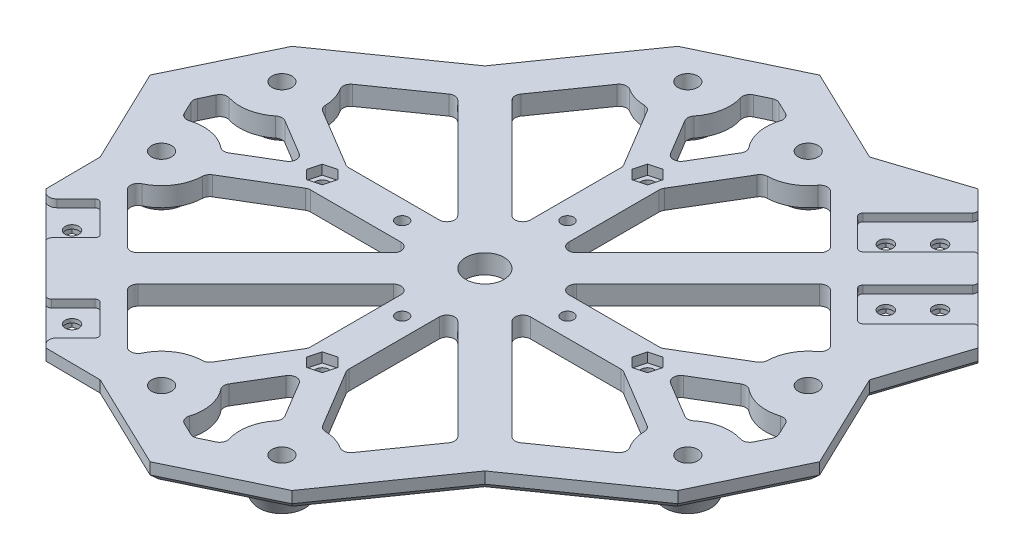
SolidWorks part; units mm, degrees
ref_plane "Front Plane" through (0, 0, 0) normal (0, 0, 1) x (1, 0, 0)
ref_plane "Top Plane" through (0, 0, 0) normal (0, 1, 0) x (1, 0, 0)
ref_plane "Right Plane" through (0, 0, 0) normal (1, 0, 0) x (0, 0, -1)
sketch "Sketch1" plane through (0, 0, 0) normal (0, 1, 0) x (1, 0, 0)
  line L0 (-15.705, 68.65) -> (15.705, 68.65) construction
  line L1 (0, 68.65) -> (0, 0) construction
  line L10 (-15.705, 68.65) -> (0, 87.35) construction
  line L11 (-25.0004, 75.3528) -> (0, 87.35)
  line L12 (0, 87.35) -> (25.0004, 75.3528)
  line L26 (-25.0004, 75.3528) -> (-15.705, 68.65) construction
  line L27 (0, 87.35) -> (15.705, 68.65) construction
  line L28 (-15.705, 68.65) -> (15.705, 68.65) construction
  line L30 (15.705, 68.65) -> (25.0004, 75.3528) construction
  line L31 (75.3528, 25.0004) -> (87.35, 0)
  line L32 (87.35, 0) -> (75.3528, -25.0004)
  line L33 (68.65, 15.705) -> (68.65, -15.705) construction
  line L34 (68.65, 15.705) -> (87.35, 0) construction
  line L36 (75.3528, 25.0004) -> (68.65, 15.705) construction
  line L37 (87.35, 0) -> (68.65, -15.705) construction
  line L38 (68.65, 15.705) -> (68.65, -15.705) construction
  line L39 (68.65, -15.705) -> (75.3528, -25.0004) construction
  line L40 (25.0004, -75.3528) -> (0, -87.35)
  line L41 (0, -87.35) -> (-25.0004, -75.3528)
  line L42 (15.705, -68.65) -> (-15.705, -68.65) construction
  line L43 (15.705, -68.65) -> (0, -87.35) construction
  line L44 (25.0004, -75.3528) -> (45.7527, -45.7527)
  line L45 (25.0004, -75.3528) -> (15.705, -68.65) construction
  line L46 (0, -87.35) -> (-15.705, -68.65) construction
  line L47 (15.705, -68.65) -> (-15.705, -68.65) construction
  line L48 (-15.705, -68.65) -> (-25.0004, -75.3528) construction
  line L49 (-75.3528, -25.0004) -> (-87.35, 0)
  line L50 (-87.35, 0) -> (-75.3528, 25.0004)
  line L51 (-68.65, -15.705) -> (-68.65, 15.705) construction
  line L52 (-68.65, -15.705) -> (-87.35, 0) construction
  line L53 (45.7527, -45.7527) -> (75.3528, -25.0004)
  line L54 (-75.3528, -25.0004) -> (-68.65, -15.705) construction
  line L55 (-87.35, 0) -> (-68.65, 15.705) construction
  line L56 (-68.65, -15.705) -> (-68.65, 15.705) construction
  line L57 (-68.65, 15.705) -> (-75.3528, 25.0004) construction
  line L58 (-75.3528, 25.0004) -> (-45.7527, 45.7527)
  line L59 (-45.7527, 45.7527) -> (-25.0004, 75.3528)
  line L62 (-75.3528, -25.0004) -> (-75.2258, -39.2695)
  line L66 (-39.2695, -75.2258) -> (-25.0004, -75.3528)
  line L67 (-75.2258, -39.2695) -> (-39.2695, -75.2258)
  line L68 (-75.3528, -25.0004) -> (-25.0004, -75.3528) construction
  line L69 (46.3472, 82.3036) -> (82.3036, 46.3472)
  line L70 (-45.7527, 45.7527) -> (45.7527, -45.7527) construction
  line L71 (25.0004, 75.3528) -> (46.3472, 82.3036)
  line L75 (82.3036, 46.3472) -> (75.3528, 25.0004)
  line L76 (64.3254, 64.3254) -> (50.1766, 50.1766) construction
  line L77 (25.0004, 75.3528) -> (75.3528, 25.0004) construction
  line L78 (-57.2477, -57.2477) -> (-50.1766, -50.1766) construction
  circle A0 centre (-15.705, 68.65) radius 2.6
  circle A1 centre (15.705, 68.65) radius 2.6
  circle A2 centre (68.65, 15.705) radius 2.6
  circle A3 centre (68.65, -15.705) radius 2.6
  circle A4 centre (15.705, -68.65) radius 2.6
  circle A5 centre (-15.705, -68.65) radius 2.6
  circle A6 centre (-68.65, -15.705) radius 2.6
  circle A7 centre (-68.65, 15.705) radius 2.6
  point P4 (0, 68.65)
  point P42 (0, 0)
  dimension "D1" = 5.2
  dimension "D2" = 31.41
  dimension "D3" = 68.65
  dimension "D5" = 24.42
  dimension "D6" = 10
  dimension "D7" = 11.46
  dimension "D8" = 36.15
  dimension "D9" = 4
  dimension "D4" = 27.73
  dimension "D12" = 50.85
  dimension "D13" = 22.45
  dimension "D15" = 50.85
extrude "Boss-Extrude1" add sketch "Sketch1" along normal blind 5
ref_axis "Axis1" through (-15.705, 5, -68.65) along (0, -1, 0)
ref_plane "Plane1" through (14.012, 0, -6.7241) normal (0.9016, 0, -0.4326) x (0, -1, 0)
sketch "Sketch4" plane through (14.012, 0, -6.7241) normal (0.9016, 0, -0.4326) x (0, -1, 0)
  line L0 (0, 73.1871) -> (4, 73.1871)
  line L1 (4, 73.1871) -> (4, 74.6871)
  line L2 (4, 74.6871) -> (0, 76.6871)
  line L3 (0, 76.6871) -> (0, 73.1871)
  line L4 (-5, 68.6871) -> (0, 68.6871) construction
  point P0 (0, 68.6871)
  dimension "D1" = 4
  dimension "D2" = 8
  dimension "D3" = 4.5
  dimension "D4" = 6
revolve "Revolve1" add sketch "Sketch4" angle 360 about axis through (-15.705, 5, -68.65) along (0, -1, 0)
ref_plane "Plane2" through (0, 0, 0) normal (1, 0, 0) x (0, 0, -1)
mirror "Mirror1" about plane through (0, 0, 0) normal (1, 0, 0) of "Revolve1"
ref_axis "Axis3" through (0, 0, 0) along (0, -1, 0)
pattern_circular "CirPattern1" count 4 every 90 about axis through (0, 0, 0) along (0, -1, 0) of "Revolve1", "Mirror1"
chamfer "Chamfer2" distance 2 angle 45 16 edges at (-32.1349, 0, 75.2893) (-12.5002, 0, 81.3514) (12.5002, 0, 81.3514) (35.3765, 0, 60.5527) (60.5527, 0, 35.3765) (81.3514, 0, 12.5002) (81.3514, 0, -12.5002) (78.8282, 0, -35.6738) (35.6738, 0, -78.8282) (12.5002, 0, -81.3514) (-12.5002, 0, -81.3514) (-35.3765, 0, -60.5527) (-60.5527, 0, -35.3765) (-81.3514, 0, -12.5002) (-81.3514, 0, 12.5002) (-75.2893, 0, 32.1349)
sketch "Sketch5" plane through (0, 0, 0) normal (0, -1, 0) x (1, 0, 0)
  line L0 (-57.2477, 57.2477) -> (64.3254, -64.3254) construction
  line L3 (44.3168, 44.3168) -> (-44.3168, -44.3168) construction
  line L4 (-21.5668, 0) -> (0, 21.5668) construction
  line L5 (0, 21.5668) -> (21.5668, 0) construction
  line L6 (21.5668, 0) -> (0, -21.5668) construction
  line L7 (0, -21.5668) -> (-21.5668, 0) construction
  line L10 (-73.2078, 41.2875) -> (-41.2875, 73.2078) construction
  line L11 (80.7169, -47.934) -> (47.934, -80.7169) construction
  circle A0 centre (0, 21.5668) radius 1.6
  circle A1 centre (-21.5668, 0) radius 1.6
  circle A2 centre (0, -21.5668) radius 1.6
  circle A3 centre (21.5668, 0) radius 1.6
  dimension "D4" = 3.2
  dimension "D1" = 30.5
  dimension "D2" = 15.25
  dimension "D3" = 15.25
extrude "Cut-Extrude1" cut sketch "Sketch5" against normal through all
sketch "Sketch6" plane through (0, 0, 0) normal (0, -1, 0) x (1, 0, 0)
  line L0 (44.3168, 44.3168) -> (-44.3168, -44.3168) construction
  line L1 (2.0412, 23.608) -> (-0.7471, 24.3551)
  line L2 (-0.7471, 24.3551) -> (-2.7884, 22.3139)
  line L3 (-2.7884, 22.3139) -> (-2.0412, 19.5255)
  line L4 (-2.0412, 19.5255) -> (0.7471, 18.7784)
  line L5 (0.7471, 18.7784) -> (2.7884, 20.8196)
  line L6 (2.7884, 20.8196) -> (2.0412, 23.608)
  line L7 (23.608, 2.0412) -> (20.8196, 2.7884)
  line L8 (20.8196, 2.7884) -> (18.7784, 0.7471)
  line L9 (18.7784, 0.7471) -> (19.5255, -2.0412)
  line L10 (19.5255, -2.0412) -> (22.3139, -2.7884)
  line L11 (22.3139, -2.7884) -> (24.3551, -0.7471)
  line L12 (24.3551, -0.7471) -> (23.608, 2.0412)
  line L13 (-19.5255, 2.0412) -> (-22.3139, 2.7884)
  line L14 (-22.3139, 2.7884) -> (-24.3551, 0.7471)
  line L15 (-24.3551, 0.7471) -> (-23.608, -2.0412)
  line L16 (-23.608, -2.0412) -> (-20.8196, -2.7884)
  line L17 (-20.8196, -2.7884) -> (-18.7784, -0.7471)
  line L18 (-18.7784, -0.7471) -> (-19.5255, 2.0412)
  line L19 (-0.7471, -18.7784) -> (-2.7884, -20.8196)
  line L20 (-2.7884, -20.8196) -> (-2.0412, -23.608)
  line L21 (-2.0412, -23.608) -> (0.7471, -24.3551)
  line L22 (0.7471, -24.3551) -> (2.7884, -22.3139)
  line L23 (2.7884, -22.3139) -> (2.0412, -19.5255)
  line L24 (2.0412, -19.5255) -> (-0.7471, -18.7784)
  circle A0 centre (0, 21.5668) radius 2.5 construction
  circle A1 centre (21.5668, 0) radius 2.5 construction
  circle A2 centre (-21.5668, 0) radius 2.5 construction
  circle A3 centre (0, -21.5668) radius 2.5 construction
  dimension "D1" = 5
extrude "Cut-Extrude2" cut sketch "Sketch6" against normal blind 2.5
sketch "Sketch8" plane through (0, 5, 0) normal (0, 1, 0) x (1, 0, 0)
  line L0 (-64.4601, -43.2469) -> (-43.2469, -64.4601) construction
  line L1 (-75.2258, -39.2695) -> (-39.2695, -75.2258) construction
  line L2 (-53.8535, -53.8535) -> (-57.2477, -57.2477) construction
  line L3 (51.9511, 66.8003) -> (66.8003, 51.9511) construction
  line L4 (44.88, 59.7292) -> (59.7292, 44.88) construction
  line L5 (82.3036, 46.3472) -> (46.3472, 82.3036) construction
  line L6 (64.3254, 64.3254) -> (59.3757, 59.3757) construction
  line L7 (59.3757, 59.3757) -> (52.3046, 52.3046) construction
  circle A0 centre (-64.4601, -43.2469) radius 1.8
  circle A1 centre (-43.2469, -64.4601) radius 1.8
  circle A2 centre (51.9511, 66.8003) radius 1.8
  circle A3 centre (44.88, 59.7292) radius 1.8
  circle A4 centre (66.8003, 51.9511) radius 1.8
  circle A5 centre (59.7292, 44.88) radius 1.8
  dimension "D1" = 3.6
  dimension "D4" = 3.6
  dimension "D2" = 4.8
  dimension "D3" = 30
  dimension "D5" = 7
  dimension "D6" = 17
  dimension "D7" = 21
  dimension "D8" = 21
extrude "Cut-Extrude3" cut sketch "Sketch8" against normal through all
sketch "Sketch9" plane through (0, 5, 0) normal (0, 1, 0) x (1, 0, 0)
  line L0 (-75.2258, -39.2695) -> (-72.9454, -41.5499) construction
  line L1 (-75.2258, -39.2695) -> (-39.2695, -75.2258) construction
  line L2 (-72.9454, -41.5499) -> (-65.8744, -34.4788)
  line L3 (-65.8744, -34.4788) -> (-57.1062, -43.2469)
  line L4 (-57.1062, -43.2469) -> (-64.1773, -50.318)
  line L5 (-64.1773, -50.318) -> (-50.318, -64.1773) construction
  line L6 (-50.318, -64.1773) -> (-43.2469, -57.1062)
  line L7 (-43.2469, -57.1062) -> (-34.4788, -65.8744)
  line L8 (-34.4788, -65.8744) -> (-41.5499, -72.9454)
  line L9 (-41.5499, -72.9454) -> (-39.2695, -75.2258) construction
  line L10 (-72.9454, -41.5499) -> (-64.1773, -50.318)
  line L11 (-50.318, -64.1773) -> (-41.5499, -72.9454)
  line L12 (46.3472, 82.3036) -> (51.8096, 76.8412) construction
  line L13 (82.3036, 46.3472) -> (46.3472, 82.3036) construction
  line L14 (51.8096, 76.8412) -> (36.1119, 61.1435)
  line L15 (36.1119, 61.1435) -> (44.88, 52.3753)
  line L16 (44.88, 52.3753) -> (60.5778, 68.0731)
  line L17 (60.5778, 68.0731) -> (68.0731, 60.5778) construction
  line L18 (68.0731, 60.5778) -> (52.3753, 44.88)
  line L19 (52.3753, 44.88) -> (61.1435, 36.1119)
  line L20 (61.1435, 36.1119) -> (76.8412, 51.8096)
  line L21 (76.8412, 51.8096) -> (82.3036, 46.3472) construction
  line L22 (51.8096, 76.8412) -> (60.5778, 68.0731)
  line L23 (68.0731, 60.5778) -> (76.8412, 51.8096)
  dimension "D1" = 12.4
  dimension "D2" = 12.4
  dimension "D3" = 19.6
  dimension "D4" = 10
  dimension "D5" = 10
  dimension "D6" = 10.6
  dimension "D7" = 12.4
  dimension "D8" = 12.4
  dimension "D9" = 22.2
  dimension "D10" = 22.2
extrude "Cut-Extrude4" cut sketch "Sketch9" against normal blind 2
sketch "Sketch11" plane through (0, 0, 0) normal (0, -1, 0) x (1, 0, 0)
  line L0 (-73.2078, 41.2875) -> (-41.2875, 73.2078) construction
  line L1 (-40.8995, 66.8076) -> (-44.1062, 67.6668)
  line L2 (-44.1062, 67.6668) -> (-46.4536, 65.3194)
  line L3 (-46.4536, 65.3194) -> (-45.5944, 62.1127)
  line L4 (-45.5944, 62.1127) -> (-42.3877, 61.2535)
  line L5 (-42.3877, 61.2535) -> (-40.0403, 63.6009)
  line L6 (-40.0403, 63.6009) -> (-40.8995, 66.8076)
  line L7 (-65.3194, 46.4536) -> (-67.6668, 44.1062)
  line L8 (-67.6668, 44.1062) -> (-66.8076, 40.8995)
  line L9 (-66.8076, 40.8995) -> (-63.6009, 40.0403)
  line L10 (-63.6009, 40.0403) -> (-61.2535, 42.3877)
  line L11 (-61.2535, 42.3877) -> (-62.1127, 45.5944)
  line L12 (-62.1127, 45.5944) -> (-65.3194, 46.4536)
  line L13 (80.7169, -47.934) -> (47.934, -80.7169) construction
  line L14 (62.0767, -42.5326) -> (58.87, -41.6734)
  line L15 (58.87, -41.6734) -> (56.5226, -44.0208)
  line L16 (56.5226, -44.0208) -> (57.3818, -47.2274)
  line L17 (57.3818, -47.2274) -> (60.5885, -48.0866)
  line L18 (60.5885, -48.0866) -> (62.9359, -45.7392)
  line L19 (62.9359, -45.7392) -> (62.0767, -42.5326)
  line L20 (69.1477, -49.6036) -> (65.9411, -48.7444)
  line L21 (65.9411, -48.7444) -> (63.5937, -51.0919)
  line L22 (63.5937, -51.0919) -> (64.4529, -54.2985)
  line L23 (64.4529, -54.2985) -> (67.6595, -55.1577)
  line L24 (67.6595, -55.1577) -> (70.007, -52.8103)
  line L25 (70.007, -52.8103) -> (69.1477, -49.6036)
  line L26 (54.2985, -64.4529) -> (51.0919, -63.5937)
  line L27 (51.0919, -63.5937) -> (48.7444, -65.9411)
  line L28 (48.7444, -65.9411) -> (49.6036, -69.1477)
  line L29 (49.6036, -69.1477) -> (52.8103, -70.007)
  line L30 (52.8103, -70.007) -> (55.1577, -67.6595)
  line L31 (55.1577, -67.6595) -> (54.2985, -64.4529)
  line L32 (47.2274, -57.3818) -> (44.0208, -56.5226)
  line L33 (44.0208, -56.5226) -> (41.6734, -58.87)
  line L34 (41.6734, -58.87) -> (42.5326, -62.0767)
  line L35 (42.5326, -62.0767) -> (45.7392, -62.9359)
  line L36 (45.7392, -62.9359) -> (48.0866, -60.5885)
  line L37 (48.0866, -60.5885) -> (47.2274, -57.3818)
  circle A0 centre (-43.2469, 64.4601) radius 2.875 construction
  circle A1 centre (-64.4601, 43.2469) radius 2.875 construction
  circle A2 centre (59.7292, -44.88) radius 2.875 construction
  circle A3 centre (66.8003, -51.9511) radius 2.875 construction
  circle A4 centre (51.9511, -66.8003) radius 2.875 construction
  circle A5 centre (44.88, -59.7292) radius 2.875 construction
  dimension "D1" = 5.75
extrude "Cut-Extrude5" cut sketch "Sketch11" against normal blind 2
fillet "Fillet1" radius 1 14 edges at (-43.2469, 4, 57.1062) (-50.318, 4, 64.1773) (-34.4788, 4, 65.8744) (-57.1062, 4, 43.2469) (-64.1773, 4, 50.318) (-65.8744, 4, 34.4788) (60.5778, 4, -68.0731) (44.88, 4, -52.3753) (76.8412, 4, -51.8096) (61.1435, 4, -36.1119) (68.0731, 4, -60.5778) (52.3753, 4, -44.88) (51.8096, 4, -76.8412) (36.1119, 4, -61.1435)
fillet "Fillet2" radius 2 2 edges at (-41.5499, 4, 72.9454) (-72.9454, 4, 41.5499)
sketch "Sketch13" plane through (0, 5, 0) normal (0, 1, 0) x (1, 0, 0)
  line L0 (-45.7527, 45.7527) -> (0, 0) construction
  line L1 (0, 0) -> (64.3254, 64.3254) construction
  line L2 (67.366, 61.2849) -> (61.2849, 67.366) construction
  circle A0 centre (0, 42.4264) radius 1.8
  circle A1 centre (42.4264, 0) radius 1.8
  circle A2 centre (0, -42.4264) radius 1.8
  circle A3 centre (-42.4264, 0) radius 1.8
  dimension "D3" = 3.6
  dimension "D1" = 30
  dimension "D2" = 30
extrude "Cut-Extrude7" cut sketch "Sketch13" against normal through all
sketch "Sketch14" plane through (0, 5, 0) normal (0, 1, 0) x (1, 0, 0)
  line L0 (67.366, 61.2849) -> (61.2849, 67.366) construction
  line L1 (3.2066, 43.2856) -> (0.8592, 45.6331)
  line L2 (0.8592, 45.6331) -> (-2.3474, 44.7738)
  line L3 (-2.3474, 44.7738) -> (-3.2066, 41.5672)
  line L4 (-3.2066, 41.5672) -> (-0.8592, 39.2198)
  line L5 (-0.8592, 39.2198) -> (2.3474, 40.079)
  line L6 (2.3474, 40.079) -> (3.2066, 43.2856)
  line L7 (43.2856, 3.2066) -> (40.079, 2.3474)
  line L8 (40.079, 2.3474) -> (39.2198, -0.8592)
  line L9 (39.2198, -0.8592) -> (41.5672, -3.2066)
  line L10 (41.5672, -3.2066) -> (44.7738, -2.3474)
  line L11 (44.7738, -2.3474) -> (45.6331, 0.8592)
  line L12 (45.6331, 0.8592) -> (43.2856, 3.2066)
  line L13 (0.8592, -39.2198) -> (-2.3474, -40.079)
  line L14 (-2.3474, -40.079) -> (-3.2066, -43.2856)
  line L15 (-3.2066, -43.2856) -> (-0.8592, -45.6331)
  line L16 (-0.8592, -45.6331) -> (2.3474, -44.7738)
  line L17 (2.3474, -44.7738) -> (3.2066, -41.5672)
  line L18 (3.2066, -41.5672) -> (0.8592, -39.2198)
  line L19 (-39.2198, 0.8592) -> (-41.5672, 3.2066)
  line L20 (-41.5672, 3.2066) -> (-44.7738, 2.3474)
  line L21 (-44.7738, 2.3474) -> (-45.6331, -0.8592)
  line L22 (-45.6331, -0.8592) -> (-43.2856, -3.2066)
  line L23 (-43.2856, -3.2066) -> (-40.079, -2.3474)
  line L24 (-40.079, -2.3474) -> (-39.2198, 0.8592)
  circle A0 centre (0, 42.4264) radius 2.875 construction
  circle A1 centre (42.4264, 0) radius 2.875 construction
  circle A2 centre (0, -42.4264) radius 2.875 construction
  circle A3 centre (-42.4264, 0) radius 2.875 construction
  point P28 (-43.1705, 2.777)
  dimension "D1" = 5.75
extrude "Cut-Extrude8" cut sketch "Sketch14" against normal blind 2.5
sketch "Sketch15" plane through (0, 5, 0) normal (0, 1, 0) x (1, 0, 0)
  line L0 (0, 0) -> (0, 21.5668) construction
  line L1 (0, 21.5668) -> (0, 42.4264) construction
  line L2 (0, 42.4264) -> (-15.705, 68.65) construction
  line L3 (0, 42.4264) -> (15.705, 68.65) construction
  line L4 (0, 0) -> (-21.5668, 0) construction
  line L5 (-21.5668, 0) -> (-42.4264, 0) construction
  line L6 (-42.4264, 0) -> (-68.65, 15.705) construction
  line L7 (-42.4264, 0) -> (-68.65, -15.705) construction
  line L8 (0, 0) -> (-45.7527, 45.7527) construction
  line L9 (0, 0) -> (64.3254, 64.3254) construction
  line L10 (67.366, 61.2849) -> (61.2849, 67.366) construction
  line L11 (0, 0) -> (-57.2477, -57.2477) construction
  line L12 (-63.4702, -51.0251) -> (-51.0251, -63.4702) construction
  line L13 (-58.8522, 24.356) -> (-44.105, 34.695)
  line L14 (-41.5427, 34.4716) -> (-15.4853, 8.4142)
  line L16 (-16.8995, 5) -> (-40.4906, 5)
  line L17 (-41.5182, 5.2842) -> (-56.6831, 14.3662)
  line L18 (-45.7527, 45.7527) -> (-75.3528, 25.0004) construction
  line L19 (-74.2699, 4.1432) -> (-75.8429, 0.8653)
  line L20 (-75.8429, -0.8653) -> (-74.2699, -4.1432)
  line L21 (-59.4711, 7.2938) -> (-50.1572, 1.7158)
  line L22 (-50.1572, -1.7158) -> (-59.4711, -7.2938)
  line L23 (-75.3528, 25.0004) -> (-87.35, 0) construction
  line L24 (-87.35, 0) -> (-75.3528, -25.0004) construction
  line L25 (-34.695, 44.105) -> (-24.356, 58.8522)
  line L26 (-14.3662, 56.6831) -> (-5.2842, 41.5182)
  line L27 (-5, 40.4906) -> (-5, 16.8995)
  line L29 (-8.4142, 15.4853) -> (-34.4716, 41.5427)
  line L30 (-25.0004, 75.3528) -> (-45.7527, 45.7527) construction
  line L31 (-4.1432, 74.2699) -> (-0.8653, 75.8429)
  line L32 (0.8653, 75.8429) -> (4.1432, 74.2699)
  line L33 (-7.2938, 59.4711) -> (-1.7158, 50.1572)
  line L34 (1.7158, 50.1572) -> (7.2938, 59.4711)
  line L35 (0, 87.35) -> (-25.0004, 75.3528) construction
  line L36 (25.0004, 75.3528) -> (0, 87.35) construction
  line L37 (-56.6831, -14.3662) -> (-41.5182, -5.2842)
  line L38 (-40.4906, -5) -> (-16.8995, -5)
  line L40 (-15.4853, -8.4142) -> (-48.7624, -41.6913)
  line L41 (-51.5908, -41.6913) -> (-64.4417, -28.8404)
  line L42 (-57.8133, -42.5398) -> (-65.1672, -35.1859) construction
  line L44 (5, 40.4906) -> (5, 16.8995)
  line L47 (8.4142, 15.4853) -> (40.1424, 47.2135)
  line L48 (40.1424, 50.0419) -> (27.6887, 62.4955)
  line L49 (36.819, 60.4364) -> (44.1729, 53.0824) construction
  line L50 (5.2842, 41.5182) -> (14.3662, 56.6831)
  line L51 (40.4906, 5) -> (16.8995, 5)
  line L52 (15.4853, 8.4142) -> (47.2135, 40.1424)
  line L53 (50.0419, 40.1424) -> (62.4955, 27.6887)
  line L54 (41.5182, 5.2842) -> (56.6831, 14.3662)
  line L55 (59.4711, -7.2938) -> (50.1572, -1.7158)
  line L56 (74.2699, -4.1432) -> (75.8429, -0.8653)
  line L57 (75.8429, 0.8653) -> (74.2699, 4.1432)
  line L58 (50.1572, 1.7158) -> (59.4711, 7.2938)
  line L59 (44.105, -34.695) -> (58.8522, -24.356)
  line L60 (15.4853, -8.4142) -> (41.5427, -34.4716)
  line L61 (40.4906, -5) -> (16.8995, -5)
  line L62 (56.6831, -14.3662) -> (41.5182, -5.2842)
  line L63 (24.356, -58.8522) -> (34.695, -44.105)
  line L64 (5.2842, -41.5182) -> (14.3662, -56.6831)
  line L65 (5, -16.8995) -> (5, -40.4906)
  line L66 (34.4716, -41.5427) -> (8.4142, -15.4853)
  line L67 (7.2938, -59.4711) -> (1.7158, -50.1572)
  line L68 (-1.7158, -50.1572) -> (-7.2938, -59.4711)
  line L69 (-0.8653, -75.8429) -> (-4.1432, -74.2699)
  line L70 (4.1432, -74.2699) -> (0.8653, -75.8429)
  line L71 (-41.6913, -51.5908) -> (-28.8404, -64.4417)
  line L72 (-8.4142, -15.4853) -> (-41.6913, -48.7624)
  line L73 (-5, -40.4906) -> (-5, -16.8995)
  line L74 (-14.3662, -56.6831) -> (-5.2842, -41.5182)
  circle A0 centre (-68.65, 15.705) radius 11 construction
  circle A1 centre (-68.65, -15.705) radius 11 construction
  circle A2 centre (-15.705, 68.65) radius 11 construction
  circle A3 centre (15.705, 68.65) radius 11 construction
  circle A4 centre (0, 42.4264) radius 5 construction
  circle A5 centre (0, 21.5668) radius 5 construction
  circle A6 centre (-21.5668, 0) radius 5 construction
  circle A7 centre (-42.4264, 0) radius 5 construction
  arc A11 (-61.7527, 7.136) -> (-71.8796, 5.1898) centre (-68.65, 15.705) cw
  arc A12 (-61.7527, -7.136) -> (-71.8796, -5.1898) centre (-68.65, -15.705) ccw
  arc A16 (-7.136, 61.7527) -> (-5.1898, 71.8796) centre (-15.705, 68.65) ccw
  arc A17 (5.1898, 71.8796) -> (7.136, 61.7527) centre (15.705, 68.65) ccw
  arc A32 (-59.4711, 7.2938) -> (-61.7527, 7.136) centre (-60.4987, 5.578) ccw
  arc A33 (-50.1572, 1.7158) -> (-50.1572, -1.7158) centre (-51.1848, 0) cw
  arc A34 (-59.4711, -7.2938) -> (-61.7527, -7.136) centre (-60.4987, -5.578) cw
  arc A35 (-74.2699, -4.1432) -> (-71.8796, -5.1898) centre (-72.4668, -3.2779) ccw
  arc A36 (-75.8429, 0.8653) -> (-75.8429, -0.8653) centre (-74.0398, 0) ccw
  arc A37 (-74.2699, 4.1432) -> (-71.8796, 5.1898) centre (-72.4668, 3.2779) cw
  arc A54 (-1.7158, 50.1572) -> (1.7158, 50.1572) centre (0, 51.1848) ccw
  arc A55 (7.2938, 59.4711) -> (7.136, 61.7527) centre (5.578, 60.4987) ccw
  arc A56 (-7.2938, 59.4711) -> (-7.136, 61.7527) centre (-5.578, 60.4987) cw
  arc A57 (4.1432, 74.2699) -> (5.1898, 71.8796) centre (3.2779, 72.4668) cw
  arc A58 (-0.8653, 75.8429) -> (0.8653, 75.8429) centre (0, 74.0398) cw
  arc A59 (-5.1898, 71.8796) -> (-4.1432, 74.2699) centre (-3.2779, 72.4668) cw
  arc A128 (-63.8925, -25.623) -> (-57.6546, -16.0241) centre (-68.65, -15.705) ccw
  arc A129 (-57.6546, 16.0241) -> (-59.3881, 21.6394) centre (-68.65, 15.705) ccw
  arc A130 (-21.6394, 59.3881) -> (-16.0241, 57.6546) centre (-15.705, 68.65) ccw
  arc A131 (24.6484, 62.2457) -> (16.0241, 57.6546) centre (15.705, 68.65) cw
  arc A132 (40.1424, 47.2135) -> (40.1424, 50.0419) centre (38.7282, 48.6277) ccw
  arc A133 (27.6887, 62.4955) -> (24.6484, 62.2457) centre (26.2745, 61.0813) ccw
  arc A134 (16.0241, 57.6546) -> (14.3662, 56.6831) centre (16.0821, 55.6555) ccw
  arc A135 (5, 40.4906) -> (5.2842, 41.5182) centre (7, 40.4906) cw
  arc A136 (8.4142, 15.4853) -> (5, 16.8995) centre (7, 16.8995) cw
  arc A137 (-5, 16.8995) -> (-8.4142, 15.4853) centre (-7, 16.8995) cw
  arc A138 (-5, 40.4906) -> (-5.2842, 41.5182) centre (-7, 40.4906) ccw
  arc A139 (-16.0241, 57.6546) -> (-14.3662, 56.6831) centre (-16.0821, 55.6555) cw
  arc A140 (-24.356, 58.8522) -> (-21.6394, 59.3881) centre (-22.7183, 57.7041) cw
  arc A141 (-34.4716, 41.5427) -> (-34.695, 44.105) centre (-33.0574, 42.9569) cw
  arc A142 (-64.4417, -28.8404) -> (-63.8925, -25.623) centre (-63.0275, -27.4262) cw
  arc A143 (-51.5908, -41.6913) -> (-48.7624, -41.6913) centre (-50.1766, -40.2771) ccw
  arc A144 (-15.4853, -8.4142) -> (-16.8995, -5) centre (-16.8995, -7) ccw
  arc A145 (-40.4906, -5) -> (-41.5182, -5.2842) centre (-40.4906, -7) ccw
  arc A146 (-40.4906, 5) -> (-41.5182, 5.2842) centre (-40.4906, 7) cw
  arc A147 (-16.8995, 5) -> (-15.4853, 8.4142) centre (-16.8995, 7) ccw
  arc A148 (-41.5427, 34.4716) -> (-44.105, 34.695) centre (-42.9569, 33.0574) ccw
  arc A149 (-59.3881, 21.6394) -> (-58.8522, 24.356) centre (-57.7041, 22.7183) cw
  arc A150 (-56.6831, 14.3662) -> (-57.6546, 16.0241) centre (-55.6555, 16.0821) cw
  arc A151 (-57.6546, -16.0241) -> (-56.6831, -14.3662) centre (-55.6555, -16.0821) cw
  arc A152 (15.4853, 8.4142) -> (16.8995, 5) centre (16.8995, 7) ccw
  arc A153 (47.2135, 40.1424) -> (50.0419, 40.1424) centre (48.6277, 38.7282) cw
  arc A154 (62.4955, 27.6887) -> (62.2457, 24.6484) centre (61.0813, 26.2745) cw
  arc A155 (62.2457, 24.6484) -> (57.6546, 16.0241) centre (68.65, 15.705) ccw
  arc A156 (57.6546, 16.0241) -> (56.6831, 14.3662) centre (55.6555, 16.0821) cw
  arc A157 (40.4906, 5) -> (41.5182, 5.2842) centre (40.4906, 7) ccw
  arc A158 (59.4711, -7.2938) -> (61.7527, -7.136) centre (60.4987, -5.578) ccw
  arc A159 (61.7527, -7.136) -> (71.8796, -5.1898) centre (68.65, -15.705) cw
  arc A160 (71.8796, -5.1898) -> (74.2699, -4.1432) centre (72.4668, -3.2779) ccw
  arc A161 (75.8429, -0.8653) -> (75.8429, 0.8653) centre (74.0398, 0) ccw
  arc A162 (74.2699, 4.1432) -> (71.8796, 5.1898) centre (72.4668, 3.2779) ccw
  arc A163 (71.8796, 5.1898) -> (61.7527, 7.136) centre (68.65, 15.705) cw
  arc A164 (59.4711, 7.2938) -> (61.7527, 7.136) centre (60.4987, 5.578) cw
  arc A165 (50.1572, -1.7158) -> (50.1572, 1.7158) centre (51.1848, 0) cw
  arc A166 (59.3881, -21.6394) -> (57.6546, -16.0241) centre (68.65, -15.705) cw
  arc A167 (58.8522, -24.356) -> (59.3881, -21.6394) centre (57.7041, -22.7183) ccw
  arc A168 (41.5427, -34.4716) -> (44.105, -34.695) centre (42.9569, -33.0574) ccw
  arc A169 (16.8995, -5) -> (15.4853, -8.4142) centre (16.8995, -7) ccw
  arc A170 (40.4906, -5) -> (41.5182, -5.2842) centre (40.4906, -7) cw
  arc A171 (57.6546, -16.0241) -> (56.6831, -14.3662) centre (55.6555, -16.0821) ccw
  arc A172 (21.6394, -59.3881) -> (24.356, -58.8522) centre (22.7183, -57.7041) ccw
  arc A173 (16.0241, -57.6546) -> (21.6394, -59.3881) centre (15.705, -68.65) cw
  arc A174 (14.3662, -56.6831) -> (16.0241, -57.6546) centre (16.0821, -55.6555) ccw
  arc A175 (5, -40.4906) -> (5.2842, -41.5182) centre (7, -40.4906) ccw
  arc A176 (5, -16.8995) -> (8.4142, -15.4853) centre (7, -16.8995) cw
  arc A177 (34.4716, -41.5427) -> (34.695, -44.105) centre (33.0574, -42.9569) cw
  arc A178 (1.7158, -50.1572) -> (-1.7158, -50.1572) centre (0, -51.1848) ccw
  arc A179 (-7.2938, -59.4711) -> (-7.136, -61.7527) centre (-5.578, -60.4987) ccw
  arc A180 (-7.136, -61.7527) -> (-5.1898, -71.8796) centre (-15.705, -68.65) cw
  arc A181 (-4.1432, -74.2699) -> (-5.1898, -71.8796) centre (-3.2779, -72.4668) cw
  arc A182 (0.8653, -75.8429) -> (-0.8653, -75.8429) centre (0, -74.0398) cw
  arc A183 (4.1432, -74.2699) -> (5.1898, -71.8796) centre (3.2779, -72.4668) ccw
  arc A184 (7.136, -61.7527) -> (5.1898, -71.8796) centre (15.705, -68.65) ccw
  arc A185 (7.2938, -59.4711) -> (7.136, -61.7527) centre (5.578, -60.4987) cw
  arc A186 (-25.623, -63.8925) -> (-16.0241, -57.6546) centre (-15.705, -68.65) cw
  arc A187 (-28.8404, -64.4417) -> (-25.623, -63.8925) centre (-27.4262, -63.0275) ccw
  arc A188 (-41.6913, -51.5908) -> (-41.6913, -48.7624) centre (-40.2771, -50.1766) cw
  arc A189 (-8.4142, -15.4853) -> (-5, -16.8995) centre (-7, -16.8995) cw
  arc A190 (-5, -40.4906) -> (-5.2842, -41.5182) centre (-7, -40.4906) cw
  arc A191 (-16.0241, -57.6546) -> (-14.3662, -56.6831) centre (-16.0821, -55.6555) ccw
  circle A192 centre (0, 0) radius 5
  point P55 (-54.8141, -4.5048)
  point P56 (25.8311, 64.3532)
  point P60 (14.9604, 57.6752)
  point P96 (-14.9604, 57.6752)
  point P102 (-60.7444, 8.0564)
  point P103 (-23.1585, 60.5602)
  point P111 (-66.7436, -26.5385)
  point P121 (-60.7444, -8.0564)
  point P124 (-73.4672, -5.8159)
  point P129 (-73.4672, 5.8159)
  point P140 (-60.5602, 23.1585)
  point P143 (-57.6752, 14.9604)
  point P147 (-57.6752, -14.9604)
  point P178 (8.0564, 60.7444)
  point P181 (-8.0564, 60.7444)
  point P184 (5.8159, 73.4672)
  point P189 (-5.8159, 73.4672)
  dimension "D1" = 22
  dimension "D2" = 10
  dimension "D28" = 2
  dimension "D29" = 2
  dimension "D30" = 10
  dimension "D32" = 2
  dimension "D26" = 2
  dimension "D3" = 5
  dimension "D4" = 10
  dimension "D5" = 5
  dimension "D6" = 5
  dimension "D7" = 5
  dimension "D8" = 10
  dimension "D9" = 10
  dimension "D10" = 2.5
  dimension "D11" = 2.5
  dimension "D12" = 10
  dimension "D13" = 5
  dimension "D14" = 5
  dimension "D15" = 5
  dimension "D16" = 2.5
  dimension "D17" = 2.5
  dimension "D18" = 10
  dimension "D19" = 10
  dimension "D20" = 5
  dimension "D21" = 5
  dimension "D22" = 5
  dimension "D23" = 5
  dimension "D24" = 5
  dimension "D25" = 5
  dimension "D27" = 5
extrude "Cut-Extrude9" cut sketch "Sketch15" against normal through all
